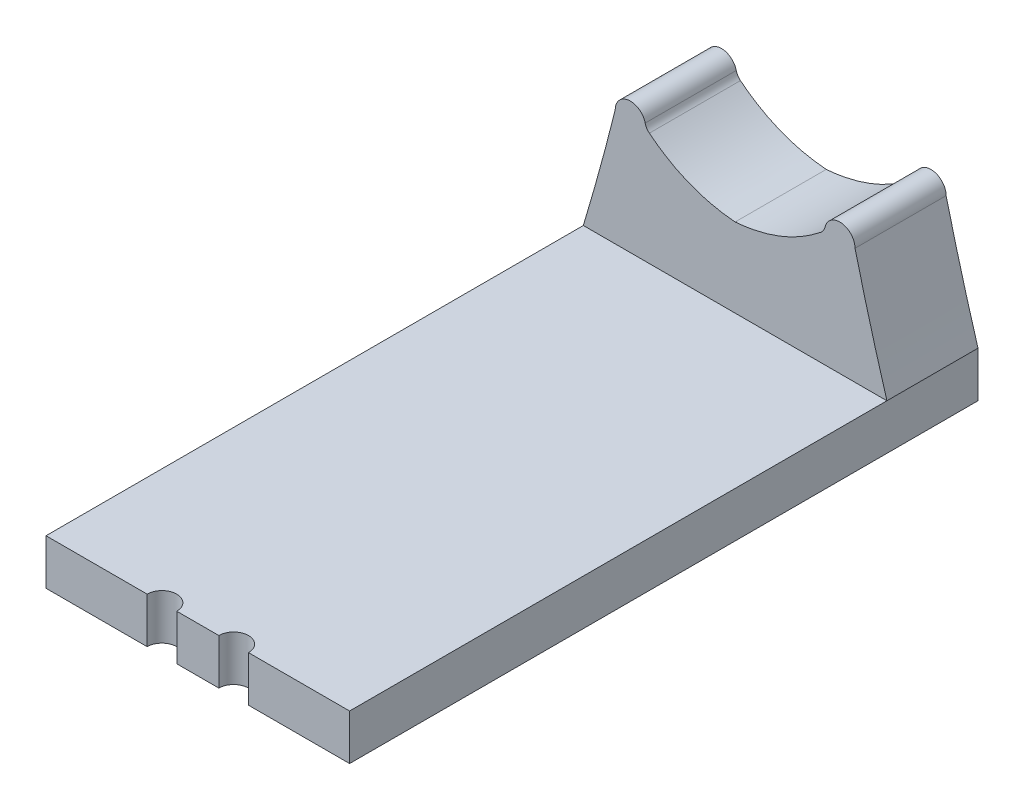
SolidWorks part; units mm, degrees
ref_plane "Front Plane" through (0, 0, 0) normal (0, 0, 1) x (1, 0, 0)
ref_plane "Top Plane" through (0, 0, 0) normal (0, 1, 0) x (1, 0, 0)
ref_plane "Right Plane" through (0, 0, 0) normal (1, 0, 0) x (0, 0, -1)
sketch "Sketch1" plane through (0, 0, 0) normal (0, 0, 1) x (1, 0, 0)
  line L0 (-996.8903, -40.64) -> (49003.1097, -40.64) construction
  line L1 (0, -1000) -> (0, 49000) construction
  line L2 (0, 0) -> (-23.4635, -40.64) construction
  line L3 (0, 0) -> (-40.64, -40.64) construction
  line L4 (-31.75, -62.23) -> (-31.75, -71.755)
  line L5 (-31.75, -71.755) -> (31.75, -71.755)
  line L6 (31.75, -62.23) -> (31.75, -71.755)
  line L7 (-957.5735, -46.99) -> (49042.4265, -46.99) construction
  circle A0 centre (0, 0) radius 40.64 construction
  arc A1 (-18.7325, -37.9449) -> (-25.0825, -37.9449) centre (-21.9075, -37.9449) ccw
  arc A2 (18.7325, -37.9449) -> (25.0825, -37.9449) centre (21.9075, -37.9449) cw
  spline S0 degree 2 poles (-18.7325, -37.9449) (-10.6333, -44.8669) (0, -45.72) knots 0 0 0 1 1 1
  spline S1 degree 2 poles (-25.0825, -37.9449) (-28.1202, -50.167) (-31.75, -62.23) knots 0 0 0 1 1 1
  spline S2 degree 2 poles (25.0825, -37.9449) (28.1202, -50.167) (31.75, -62.23) knots 0 0 0 1 1 1
  spline S3 degree 2 poles (18.7325, -37.9449) (10.6333, -44.8669) (0, -45.72) knots 0 0 0 1 1 1
  point P13 (0, -71.755)
  dimension "D1" = 81.28
  dimension "D3" = 6.35
  dimension "D5" = 5.08
  dimension "D2" = 30
  dimension "D4" = 45
  dimension "D6" = 31.75
  dimension "D7" = 9.525
  dimension "D8" = 21.59
  dimension "D9" = 6.35
extrude "Boss-Extrude1" add sketch "Sketch1" along normal mid plane 19.05
sketch "Sketch2" plane through (0, 0, 0) normal (0, 0, 1) x (1, 0, 0)
  line L1 (-31.75, -62.23) -> (31.75, -62.23)
  line L2 (-31.75, -62.23) -> (-31.75, -71.755)
  line L3 (-31.75, -71.755) -> (31.75, -71.755)
  line L4 (31.75, -62.23) -> (31.75, -71.755)
extrude "Boss-Extrude2" add sketch "Sketch2" along normal blind 121.92
fillet "Fillet2" radius 2.54 2 edges at (18.7325, -37.9449, 0) (-18.7325, -37.9449, 0)
sketch "Sketch3" plane through (0, -62.23, 0) normal (0, 1, 0) x (1, 0, 0)
  line L0 (31.75, -121.92) -> (-31.75, -121.92) construction
  line L1 (0, -9.525) -> (0, 9.525) construction
  circle A0 centre (7.5, -121.92) radius 3.1
  circle A1 centre (-7.5, -121.92) radius 3.1
  dimension "D1" = 6.2
  dimension "D2" = 7.5
extrude "Cut-Extrude1" cut sketch "Sketch3" against normal through all
ref_plane "wheel_tangent_plane" through (0, -40.64, 0) normal (0, 1, 0) x (1, 0, 0)
